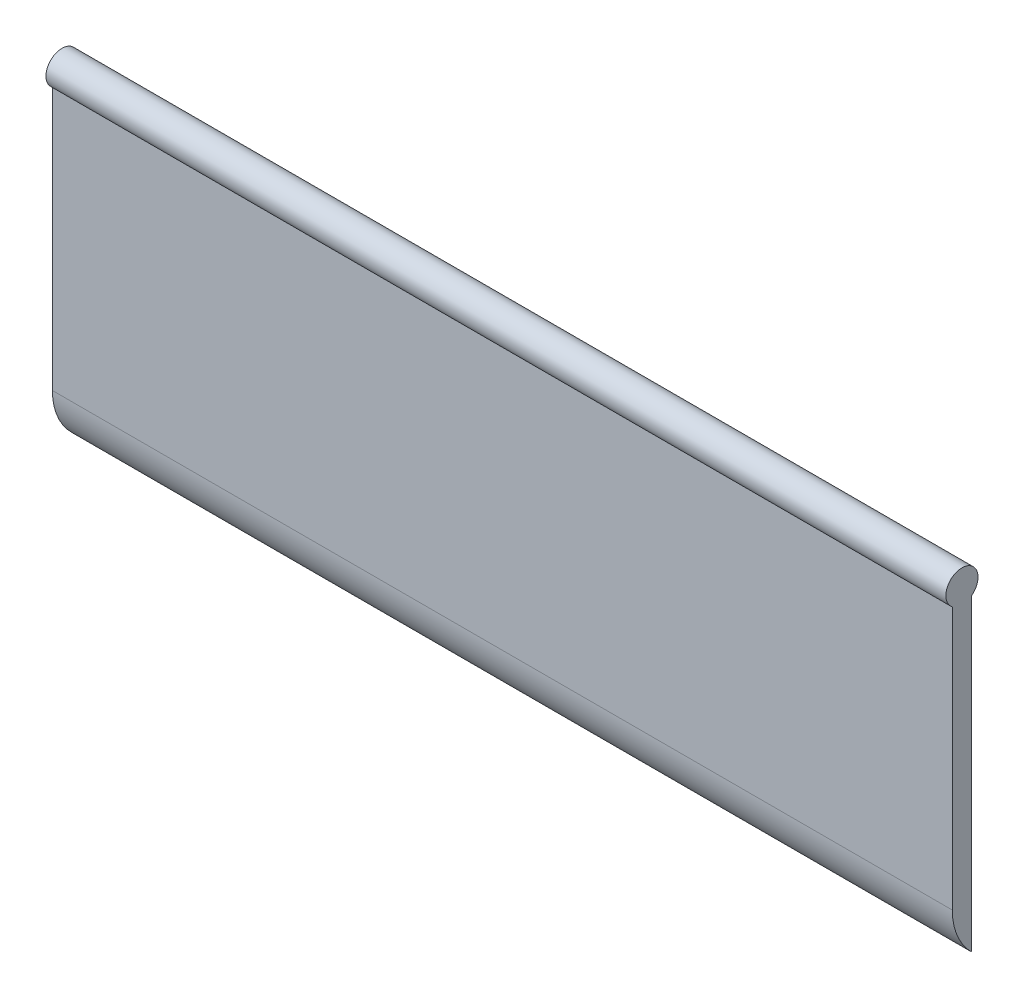
SolidWorks part; units mm, degrees
ref_plane "Front Plane" through (0, 0, 0) normal (0, 0, 1) x (1, 0, 0)
ref_plane "Top Plane" through (0, 0, 0) normal (0, 1, 0) x (1, 0, 0)
ref_plane "Right Plane" through (0, 0, 0) normal (1, 0, 0) x (0, 0, -1)
sketch "Sketch1" plane through (0, 0, 0) normal (1, 0, 0) x (0, 0, -1)
  line L1 (0, 0) -> (3, 0)
  line L2 (0, 0) -> (0, 50)
  line L3 (0, 50) -> (3, 50)
  line L4 (3, 0) -> (3, 50)
  circle A0 centre (1.5, 50) radius 2.5
  point P9 (0, 3)
  dimension "D1" = 5
  dimension "D2" = 3
  dimension "D3" = 50
extrude "Boss-Extrude1" add sketch "Sketch1" along normal blind 140 contours L4 A0 L2 L3 | L2 A0 L4 L3 | A0 L2 L1 L4 region at (0, 23.8299, -1.5) region at (0, 50.6541, -1.5) region at (0, 48.8251, -1.5)
fillet "Fillet1" radius 10 1 edges at (70, 0, 0)
